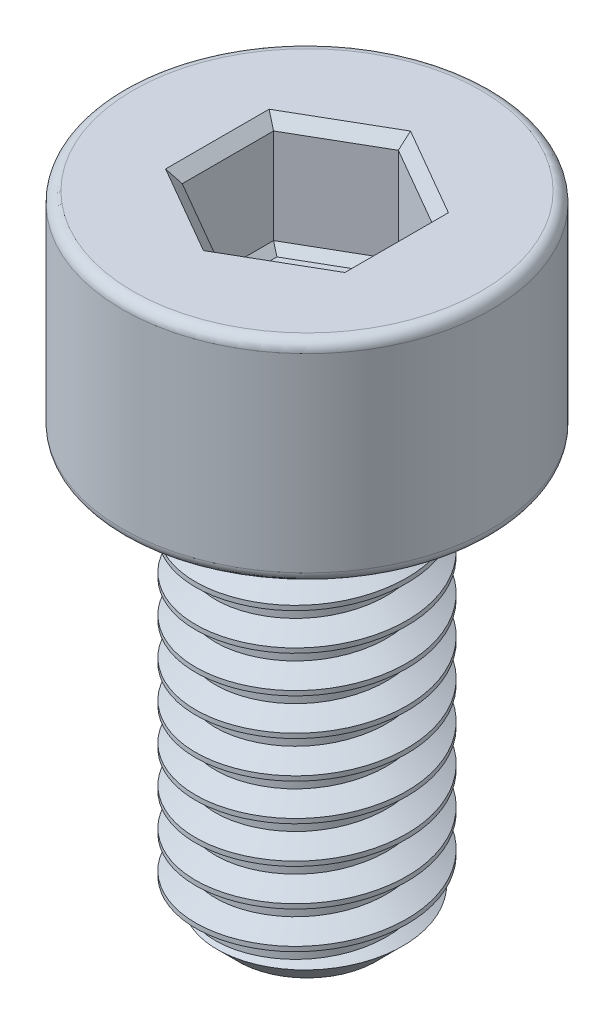
SolidWorks part; units mm, degrees
material "AISI Type A2 Tool Steel"
ref_plane "Front Plane" through (0, 0, 0) normal (0, 0, 1) x (1, 0, 0)
ref_plane "Top Plane" through (0, 0, 0) normal (0, 1, 0) x (1, 0, 0)
ref_plane "Right Plane" through (0, 0, 0) normal (1, 0, 0) x (0, 0, -1)
sketch "Sketch1" plane through (0, 0, 0) normal (0, 1, 0) x (1, 0, 0)
  circle A0 centre (0, 0) radius 2
  dimension "D1" = 4
extrude "Boss-Extrude1" add sketch "Sketch1" along normal blind 8
thread "Thread1" pitch 0.7 method cut profile "Thread Profile1" start angle 0, offset 1, length 0, pitch 0.7, diameter 4
ref_plane "Plane1" through (2, -1, 0) normal (0, 0, 1) x (1, 0, 0)
sketch "Thread Profile1" plane through (2, -1, 0) normal (0, 0, 1) x (1, 0, 0)
  line L0 (0, 0) -> (0, 0.7) construction
  line L11 (0, 0) -> (0, 0.6125)
  line L12 (0, 0.6125) -> (-0.3789, 0.3937)
  line L13 (-0.3789, 0.3937) -> (-0.3789, 0.2187)
  line L15 (-0.3789, 0.2187) -> (0, 0)
  line L17 (-0.3789, 0.3062) -> (0, 0.3062) construction
  point P2 (0, 0)
  dimension "Pitch" = 0.7
  dimension "Profile_Angle" = 60
  dimension "Profile_Land" = 0.175
  dimension "Profile_Height" = 0.3789
sketch "Sketch4" plane through (0, 8, 0) normal (0, -1, 0) x (-1, 0, 0)
  circle A0 centre (0, 0) radius 3.5
  dimension "D1" = 7
extrude "Boss-Extrude2" add sketch "Sketch4" against normal blind 4
fillet "Fillet1" radius 0.2 2 edges at (0, 8, -3.5) (0, 12, -3.5)
sketch "Sketch6" plane through (0, 0, 0) normal (0, 0, 1) x (1, 0, 0)
  line L0 (0, 0) -> (2.01, 0) construction
  line L1 (2.01, 0) -> (2.01, 0.7)
  line L2 (2.01, 0.7) -> (1.31, 0)
  line L3 (1.31, 0) -> (2.01, 0)
  line L4 (0, 0) -> (0, 0.3482) construction
  dimension "D1" = 0.7
  dimension "D2" = 45
  dimension "D3" = 2.01
revolve "Cut-Revolve1" cut sketch "Sketch6" angle 360 about L4
sketch "Sketch7" plane through (0, 12, 0) normal (0, 1, 0) x (1, 0, 0)
  line L1 (0, 1.7321) -> (-1.5, 0.866)
  line L2 (-1.5, 0.866) -> (-1.5, -0.866)
  line L3 (-1.5, -0.866) -> (0, -1.7321)
  line L4 (0, -1.7321) -> (1.5, -0.866)
  line L5 (1.5, -0.866) -> (1.5, 0.866)
  line L6 (1.5, 0.866) -> (0, 1.7321)
  circle A0 centre (0, 0) radius 1.5 construction
  dimension "D1" = 3
extrude "Cut-Extrude1" cut sketch "Sketch7" against normal blind 2
chamfer "Chamfer1" distance 0.2 angle 45 6 edges at (-1.5, 12, 0) (-0.75, 12, 1.299) (0.75, 12, 1.299) (1.5, 12, 0) (0.75, 12, -1.299) (-0.75, 12, -1.299)
sketch "Sketch8" plane through (0, 10, 0) normal (0, 1, 0) x (1, 0, 0)
  line L1 (0, 1.7321) -> (-1.5, 0.866)
  line L2 (-1.5, 0.866) -> (-1.5, -0.866)
  line L3 (-1.5, -0.866) -> (0, -1.7321)
  line L4 (0, -1.7321) -> (1.5, -0.866)
  line L5 (1.5, -0.866) -> (1.5, 0.866)
  line L6 (1.5, 0.866) -> (0, 1.7321)
  circle A0 centre (0, 0) radius 1.5 construction
extrude "Cut-Extrude2" cut sketch "Sketch8" against normal blind 0.15 draft 45
